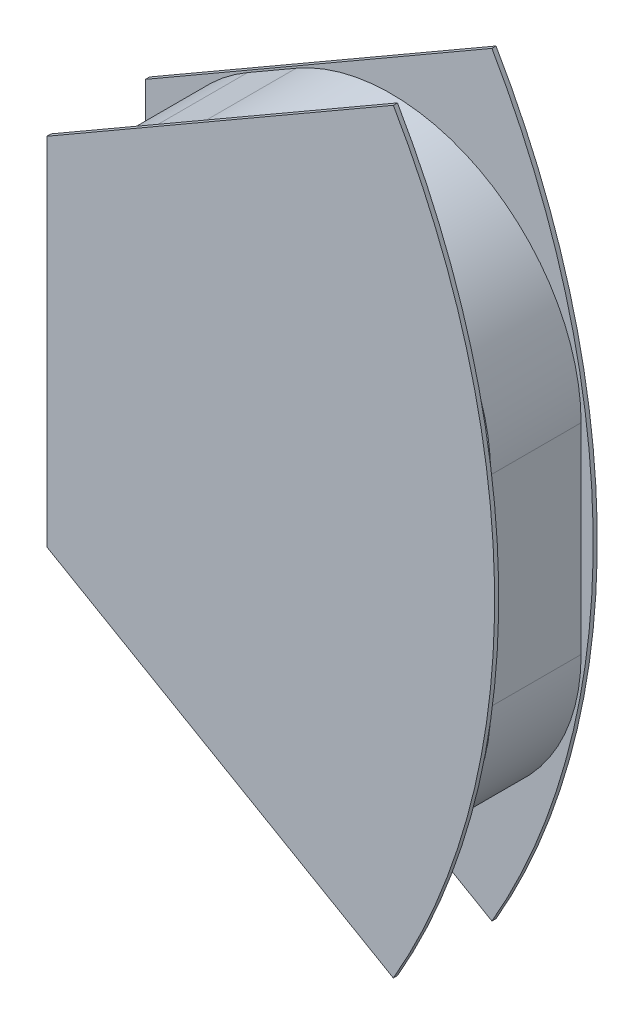
SolidWorks part; units mm, degrees
note: The reader was unsure of these and kept them because the rebuilt part matched: shared geometry of "Sketch3<3>".
ref_plane "Front Plane" through (0, 0, 0) normal (0, 0, 1) x (1, 0, 0)
ref_plane "Top Plane" through (0, 0, 0) normal (0, 1, 0) x (1, 0, 0)
ref_plane "Right Plane" through (0, 0, 0) normal (1, 0, 0) x (0, 0, -1)
sketch "Sketch2" plane through (0, 0, 0) normal (0, 0, 1) x (1, 0, 0)
  line L0 (0, 0) -> (0, -184) construction
  line L1 (-159.3487, -92) -> (0, 0) construction
  line L2 (159.3487, -92) -> (75, -43.3013)
  line L3 (75, 43.3013) -> (75, -43.3013)
  line L4 (0, 0) -> (75, 43.3013) construction
  line L5 (75, 43.3013) -> (159.3487, 92)
  line L6 (75, -43.3013) -> (0, 0) construction
  line L7 (0, 0) -> (-159.3487, 92) construction
  line L8 (0, 184) -> (0, 0) construction
  arc A0 (0, 184) -> (-159.3487, 92) centre (0, 0) ccw construction
  arc A1 (159.3487, 92) -> (0, 184) centre (0, 0) ccw construction
  arc A2 (0, -184) -> (159.3487, -92) centre (0, 0) ccw construction
  arc A3 (159.3487, -92) -> (159.3487, 92) centre (0, 0) ccw
  arc A4 (-159.3487, -92) -> (0, -184) centre (0, 0) ccw construction
  arc A5 (-159.3487, 92) -> (-159.3487, -92) centre (0, 0) ccw construction
  arc A6 (170.1845, -69.9516) -> (170.1845, 69.9516) centre (0, 0) ccw construction
  point P8 (0, -92)
  point P11 (0, -92)
  dimension "D1" = 60
  dimension "D2" = 60
  dimension "D3" = 75
extrude "Boss-Extrude1" add sketch "Sketch2" along normal blind 1 from offset 20
sketch "Sketch3" plane through (0, 0, 21) normal (0, 0, 1) x (1, 0, 0)
  line L0 (124.5, 5.5714) -> (134.3125, 5.5714) construction
  line L1 (123, -18.4752) -> (134.8125, -25.2951)
  line L2 (123, 18.4752) -> (134.8125, 25.2951)
  line L3 (135.3125, -24.4291) -> (135.3125, 24.4291) construction
  line L4 (134.3125, -22.6971) -> (134.3125, 22.6971)
  line L5 (136.3125, -24.4291) -> (136.3125, 24.4291)
  line L6 (134.5742, 22.8482) -> (122.5, 15.8771)
  line L7 (122.5, 15.8771) -> (122.5, -15.8771)
  line L8 (122.5, -15.8771) -> (134.5742, -22.8482)
  line L9 (134.5742, 22.8482) -> (124.5, 17.0318) construction
  line L10 (122.5, 15.8771) -> (122.5, -15.8771) construction
  line L11 (122.5, -15.8771) -> (123.5, -16.4545) construction
  line L12 (0, 0) -> (217.8018, 0) construction
  line L13 (122.5, -15.8771) -> (123.5, -16.4545) construction
  line L14 (123.5, -17.6092) -> (123.5, 17.6092) construction
  line L15 (122.5, -17.6092) -> (122.5, 17.6092)
  line L16 (124.5, -17.0318) -> (124.5, 17.0318)
  line L17 (124.5, 17.0318) -> (134.5742, 22.8482)
  line L18 (124.5, 17.0318) -> (124.5, 17.6092) construction
  line L19 (123.5, 16.4545) -> (122.5, 15.8771) construction
  line L20 (122.5, 15.8771) -> (123.5, 16.4545) construction
  line L21 (123.5, 16.4545) -> (124.5, 17.0318) construction
  line L22 (124.5, 17.0318) -> (123.5, 16.4545) construction
  line L23 (134.3125, 22.6971) -> (134.3125, 24.4291) construction
  line L24 (134.5742, 22.8482) -> (135.3125, 23.2744) construction
  line L25 (135.3125, 23.2744) -> (136.3125, 23.8518) construction
  line L26 (123.5, -16.4545) -> (124.5, -17.0318) construction
  line L27 (124.5, -17.0318) -> (134.3125, -22.6971)
  line L28 (123.5, -16.4545) -> (124.5, -17.0318) construction
  line L29 (124.5, -17.0318) -> (134.3125, -22.6971) construction
  line L30 (124.5, -17.6092) -> (124.5, -17.0318) construction
  line L31 (134.3125, -24.4291) -> (134.3125, -22.6971) construction
  line L32 (134.5742, -22.8482) -> (135.3125, -23.2744) construction
  line L33 (135.3125, -23.2744) -> (136.3125, -23.8518) construction
  line L34 (134.3125, -22.6971) -> (134.5742, -22.8482) construction
  line L35 (134.3125, -22.6971) -> (134.5742, -22.8482) construction
  circle A0 centre (129.4062, 0) radius 3.1
  arc A1 (134.8125, -25.2951) -> (136.3125, -24.4291) centre (135.3125, -24.4291) ccw
  arc A2 (134.5742, -22.8482) -> (134.5742, 22.8482) centre (0, 0) ccw
  arc A3 (134.5742, -22.8482) -> (134.5742, 22.8482) centre (0, 0) ccw construction
  arc A4 (136.3125, 24.4291) -> (134.8125, 25.2951) centre (135.3125, 24.4291) ccw
  arc A5 (122.5, -17.6092) -> (123, -18.4752) centre (123.5, -17.6092) ccw
  arc A6 (123, 18.4752) -> (122.5, 17.6092) centre (123.5, 17.6092) ccw
  arc A7 (124.5, 17.6092) -> (123, 18.4752) centre (123.5, 17.6092) ccw construction
  arc A8 (134.8125, 25.2951) -> (134.3125, 24.4291) centre (135.3125, 24.4291) ccw construction
  arc A9 (123, -18.4752) -> (124.5, -17.6092) centre (123.5, -17.6092) ccw construction
  arc A10 (134.3125, -24.4291) -> (134.8125, -25.2951) centre (135.3125, -24.4291) ccw construction
  point P2 (135.3125, 0)
  point P11 (129.4062, 5.5714)
  point P16 (123.5, 0)
  dimension "D4" = 6.2
  dimension "D2" = 2
  dimension "D3" = 2
  dimension "D1" = 47.5
extrude "Boss-Extrude2" add sketch "Sketch3" along normal blind 22
extrude "Cut-Extrude1" cut sketch "Sketch3<3>" against normal blind 10 contours A0
sketch "Sketch3<3>" plane through (0, 0, 21) normal (0, 0, 1) x (1, 0, 0) same geometry as "Sketch3"
sketch "Sketch4" plane through (0, 0, 21) normal (0, 0, 1) x (1, 0, 0)
  circle A0 centre (129.4062, 0) radius 6.9062
  circle A1 centre (129.4062, 0) radius 3.1
extrude "Boss-Extrude3" add sketch "Sketch4" along normal up to surface (22 mm away) up to face at (129.4062, 0, 43)
sketch "Sketch5" plane through (0, 0, 21) normal (0, 0, 1) x (1, 0, 0)
  line L6 (125, 16.7432) -> (125, 5.9529)
  line L7 (133.8125, 5.9529) -> (133.8125, 21.831)
  line L8 (133.8125, 21.831) -> (125, 16.7432)
  line L9 (125, 16.7432) -> (125, 5.9529)
  line L10 (133.8125, 5.9529) -> (133.8125, 21.831)
  line L11 (133.8125, 21.831) -> (125, 16.7432)
  line L15 (133.8125, -21.831) -> (133.8125, -5.9529)
  line L16 (125, -5.9529) -> (125, -16.7432)
  line L17 (125, -16.7432) -> (133.8125, -21.831)
  line L18 (133.8125, -21.831) -> (133.8125, -5.9529)
  line L19 (125, -5.9529) -> (125, -16.7432)
  line L20 (125, -16.7432) -> (133.8125, -21.831)
  arc A2 (133.8125, 5.9529) -> (125, 5.9529) centre (129.4062, 0) ccw
  arc A3 (133.8125, 5.9529) -> (125, 5.9529) centre (129.4062, 0) ccw
  arc A5 (125, -5.9529) -> (133.8125, -5.9529) centre (129.4062, 0) ccw
  arc A6 (125, -5.9529) -> (133.8125, -5.9529) centre (129.4062, 0) ccw
  dimension "D1" = 0.5
  dimension "D2" = 0.5
extrude "Boss-Extrude4" add sketch "Sketch5" along normal blind 22 from offset 1 separate body
sketch "Sketch6" plane through (0, 0, 44) normal (0, 0, 1) x (1, 0, 0)
  line L3 (159.3487, 92) -> (75, 43.3013)
  line L4 (75, 43.3013) -> (75, -43.3013)
  line L5 (75, -43.3013) -> (159.3487, -92)
  line L6 (159.3487, 92) -> (75, 43.3013)
  line L7 (75, 43.3013) -> (75, -43.3013)
  line L8 (75, -43.3013) -> (159.3487, -92)
  arc A1 (159.3487, -92) -> (159.3487, 92) centre (0, 0) ccw
  arc A2 (159.3487, -92) -> (159.3487, 92) centre (0, 0) ccw
  dimension "D1" = 0
extrude "Boss-Extrude5" add sketch "Sketch6" along normal blind 1
sketch "Sketch7" plane through (0, 0, 21) normal (0, 0, 1) x (1, 0, 0)
  line L13 (77.25, 17.6092) -> (77.25, -17.6092)
  line L14 (100.375, -57.6629) -> (112.1875, -64.4828)
  line L15 (181.5625, -24.4291) -> (181.5625, 24.4291)
  line L16 (112.1875, 64.4828) -> (100.375, 57.6629)
  line L17 (122.25, 17.6092) -> (122.25, -17.6092)
  line L18 (122.875, -18.6917) -> (134.6875, -25.5117)
  line L19 (136.5625, -24.4291) -> (136.5625, 24.4291)
  line L20 (134.6875, 25.5117) -> (122.875, 18.6917)
  line L21 (122.25, 17.6092) -> (122.25, -17.6092)
  line L22 (122.875, -18.6917) -> (134.6875, -25.5117)
  line L23 (136.5625, -24.4291) -> (136.5625, 24.4291)
  line L24 (134.6875, 25.5117) -> (122.875, 18.6917)
  arc A7 (100.375, 57.6629) -> (77.25, 17.6092) centre (123.5, 17.6092) ccw
  arc A8 (77.25, -17.6092) -> (100.375, -57.6629) centre (123.5, -17.6092) ccw
  arc A9 (112.1875, -64.4828) -> (181.5625, -24.4291) centre (135.3125, -24.4291) ccw
  arc A10 (181.5625, 24.4291) -> (112.1875, 64.4828) centre (135.3125, 24.4291) ccw
  arc A11 (122.875, 18.6917) -> (122.25, 17.6092) centre (123.5, 17.6092) ccw
  arc A12 (122.25, -17.6092) -> (122.875, -18.6917) centre (123.5, -17.6092) ccw
  arc A13 (134.6875, -25.5117) -> (136.5625, -24.4291) centre (135.3125, -24.4291) ccw
  arc A14 (136.5625, 24.4291) -> (134.6875, 25.5117) centre (135.3125, 24.4291) ccw
  arc A15 (122.875, 18.6917) -> (122.25, 17.6092) centre (123.5, 17.6092) ccw
  arc A16 (122.25, -17.6092) -> (122.875, -18.6917) centre (123.5, -17.6092) ccw
  arc A17 (134.6875, -25.5117) -> (136.5625, -24.4291) centre (135.3125, -24.4291) ccw
  arc A18 (136.5625, 24.4291) -> (134.6875, 25.5117) centre (135.3125, 24.4291) ccw
  dimension "D1" = 45
  dimension "D2" = 0.25
extrude "Boss-Extrude6" add sketch "Sketch7" along normal blind 22 from offset 0.5 separate body contours L15 A10 L16 A7 L13 A8 L14 A9 A18 L23 A17 L22 A16 L21 A15 L24
sketch "Sketch8" plane through (0, 0, 43.5) normal (0, 0, 1) x (1, 0, 0)
  line L0 (139.8625, -24.4291) -> (139.8625, 24.4291)
  line L1 (133.0375, 28.3695) -> (121.225, 21.5496)
  line L2 (118.95, 17.6092) -> (118.95, -17.6092)
  line L3 (121.225, -21.5496) -> (133.0375, -28.3695)
  line L4 (141.5125, -24.4291) -> (141.5125, 24.4291)
  line L5 (132.2125, 29.7985) -> (120.4, 22.9785)
  line L6 (117.3, 17.6092) -> (117.3, -17.6092)
  line L7 (120.4, -22.9785) -> (132.2125, -29.7985)
  line L8 (122.05, -20.1207) -> (133.8625, -26.9406)
  line L9 (120.6, 17.6092) -> (120.6, -17.6092)
  line L10 (133.8625, 26.9406) -> (122.05, 20.1207)
  line L11 (138.2125, -24.4291) -> (138.2125, 24.4291)
  line L12 (122.05, -20.1207) -> (133.8625, -26.9406)
  line L13 (120.6, 17.6092) -> (120.6, -17.6092)
  line L14 (133.8625, 26.9406) -> (122.05, 20.1207)
  line L15 (138.2125, -24.4291) -> (138.2125, 24.4291)
  line L16 (143.1625, -24.4291) -> (143.1625, 24.4291)
  line L17 (131.3875, 31.2274) -> (119.575, 24.4075)
  line L18 (115.65, 17.6092) -> (115.65, -17.6092)
  line L19 (119.575, -24.4075) -> (131.3875, -31.2274)
  line L20 (144.8125, -24.4291) -> (144.8125, 24.4291)
  line L21 (130.5625, 32.6564) -> (118.75, 25.8364)
  line L22 (114, 17.6092) -> (114, -17.6092)
  line L23 (118.75, -25.8364) -> (130.5625, -32.6564)
  line L24 (146.4625, -24.4291) -> (146.4625, 24.4291)
  line L25 (129.7375, 34.0853) -> (117.925, 27.2654)
  line L26 (112.35, 17.6092) -> (112.35, -17.6092)
  line L27 (117.925, -27.2654) -> (129.7375, -34.0853)
  line L28 (148.1125, -24.4291) -> (148.1125, 24.4291)
  line L29 (128.9125, 35.5142) -> (117.1, 28.6943)
  line L30 (110.7, 17.6092) -> (110.7, -17.6092)
  line L31 (117.1, -28.6943) -> (128.9125, -35.5142)
  line L32 (149.7625, -24.4291) -> (149.7625, 24.4291)
  line L33 (128.0875, 36.9432) -> (116.275, 30.1233)
  line L34 (109.05, 17.6092) -> (109.05, -17.6092)
  line L35 (116.275, -30.1233) -> (128.0875, -36.9432)
  line L36 (151.4125, -24.4291) -> (151.4125, 24.4291)
  line L37 (127.2625, 38.3721) -> (115.45, 31.5522)
  line L38 (107.4, 17.6092) -> (107.4, -17.6092)
  line L39 (115.45, -31.5522) -> (127.2625, -38.3721)
  line L40 (153.0625, -24.4291) -> (153.0625, 24.4291)
  line L41 (126.4375, 39.8011) -> (114.625, 32.9811)
  line L42 (105.75, 17.6092) -> (105.75, -17.6092)
  line L43 (114.625, -32.9811) -> (126.4375, -39.8011)
  line L44 (154.7125, -24.4291) -> (154.7125, 24.4291)
  line L45 (125.6125, 41.23) -> (113.8, 34.4101)
  line L46 (104.1, 17.6092) -> (104.1, -17.6092)
  line L47 (113.8, -34.4101) -> (125.6125, -41.23)
  line L48 (156.3625, -24.4291) -> (156.3625, 24.4291)
  line L49 (124.7875, 42.659) -> (112.975, 35.839)
  line L50 (102.45, 17.6092) -> (102.45, -17.6092)
  line L51 (112.975, -35.839) -> (124.7875, -42.659)
  line L52 (158.0125, -24.4291) -> (158.0125, 24.4291)
  line L53 (123.9625, 44.0879) -> (112.15, 37.268)
  line L54 (100.8, 17.6092) -> (100.8, -17.6092)
  line L55 (112.15, -37.268) -> (123.9625, -44.0879)
  line L56 (159.6625, -24.4291) -> (159.6625, 24.4291)
  line L57 (123.1375, 45.5168) -> (111.325, 38.6969)
  line L58 (99.15, 17.6092) -> (99.15, -17.6092)
  line L59 (111.325, -38.6969) -> (123.1375, -45.5168)
  line L60 (161.3125, -24.4291) -> (161.3125, 24.4291)
  line L61 (122.3125, 46.9458) -> (110.5, 40.1258)
  line L62 (97.5, 17.6092) -> (97.5, -17.6092)
  line L63 (110.5, -40.1258) -> (122.3125, -46.9458)
  line L64 (162.9625, -24.4291) -> (162.9625, 24.4291)
  line L65 (121.4875, 48.3747) -> (109.675, 41.5548)
  line L66 (95.85, 17.6092) -> (95.85, -17.6092)
  line L67 (109.675, -41.5548) -> (121.4875, -48.3747)
  line L68 (94.2, 17.6092) -> (94.2, -17.6092)
  line L69 (108.85, -42.9837) -> (120.6625, -49.8037)
  line L70 (164.6125, -24.4291) -> (164.6125, 24.4291)
  line L71 (120.6625, 49.8037) -> (108.85, 42.9837)
  line L72 (92.55, 17.6092) -> (92.55, -17.6092)
  line L73 (108.025, -44.4127) -> (119.8375, -51.2326)
  line L74 (166.2625, -24.4291) -> (166.2625, 24.4291)
  line L75 (119.8375, 51.2326) -> (108.025, 44.4127)
  line L76 (90.9, 17.6092) -> (90.9, -17.6092)
  line L77 (107.2, -45.8416) -> (119.0125, -52.6616)
  line L78 (167.9125, -24.4291) -> (167.9125, 24.4291)
  line L79 (119.0125, 52.6616) -> (107.2, 45.8416)
  line L80 (89.25, 17.6092) -> (89.25, -17.6092)
  line L81 (106.375, -47.2706) -> (118.1875, -54.0905)
  line L82 (169.5625, -24.4291) -> (169.5625, 24.4291)
  line L83 (118.1875, 54.0905) -> (106.375, 47.2706)
  line L84 (87.6, 17.6092) -> (87.6, -17.6092)
  line L85 (105.55, -48.6995) -> (117.3625, -55.5194)
  line L86 (171.2125, -24.4291) -> (171.2125, 24.4291)
  line L87 (117.3625, 55.5194) -> (105.55, 48.6995)
  line L88 (85.95, 17.6092) -> (85.95, -17.6092)
  line L89 (104.725, -50.1284) -> (116.5375, -56.9484)
  line L90 (172.8625, -24.4291) -> (172.8625, 24.4291)
  line L91 (116.5375, 56.9484) -> (104.725, 50.1284)
  line L92 (84.3, 17.6092) -> (84.3, -17.6092)
  line L93 (103.9, -51.5574) -> (115.7125, -58.3773)
  line L94 (174.5125, -24.4291) -> (174.5125, 24.4291)
  line L95 (115.7125, 58.3773) -> (103.9, 51.5574)
  line L96 (82.65, 17.6092) -> (82.65, -17.6092)
  line L97 (103.075, -52.9863) -> (114.8875, -59.8063)
  line L98 (176.1625, -24.4291) -> (176.1625, 24.4291)
  line L99 (114.8875, 59.8063) -> (103.075, 52.9863)
  line L100 (81, 17.6092) -> (81, -17.6092)
  line L101 (102.25, -54.4153) -> (114.0625, -61.2352)
  line L102 (177.8125, -24.4291) -> (177.8125, 24.4291)
  line L103 (114.0625, 61.2352) -> (102.25, 54.4153)
  line L104 (79.35, 17.6092) -> (79.35, -17.6092)
  line L105 (101.425, -55.8442) -> (113.2375, -62.6641)
  line L106 (179.4625, -24.4291) -> (179.4625, 24.4291)
  line L107 (113.2375, 62.6641) -> (101.425, 55.8442)
  arc A0 (133.0375, -28.3695) -> (139.8625, -24.4291) centre (135.3125, -24.4291) ccw
  arc A1 (139.8625, 24.4291) -> (133.0375, 28.3695) centre (135.3125, 24.4291) ccw
  arc A2 (121.225, 21.5496) -> (118.95, 17.6092) centre (123.5, 17.6092) ccw
  arc A3 (118.95, -17.6092) -> (121.225, -21.5496) centre (123.5, -17.6092) ccw
  arc A4 (132.2125, -29.7985) -> (141.5125, -24.4291) centre (135.3125, -24.4291) ccw
  arc A5 (141.5125, 24.4291) -> (132.2125, 29.7985) centre (135.3125, 24.4291) ccw
  arc A6 (120.4, 22.9785) -> (117.3, 17.6092) centre (123.5, 17.6092) ccw
  arc A7 (117.3, -17.6092) -> (120.4, -22.9785) centre (123.5, -17.6092) ccw
  arc A8 (133.8625, -26.9406) -> (138.2125, -24.4291) centre (135.3125, -24.4291) ccw
  arc A9 (120.6, -17.6092) -> (122.05, -20.1207) centre (123.5, -17.6092) ccw
  arc A10 (122.05, 20.1207) -> (120.6, 17.6092) centre (123.5, 17.6092) ccw
  arc A11 (138.2125, 24.4291) -> (133.8625, 26.9406) centre (135.3125, 24.4291) ccw
  arc A12 (133.8625, -26.9406) -> (138.2125, -24.4291) centre (135.3125, -24.4291) ccw
  arc A13 (120.6, -17.6092) -> (122.05, -20.1207) centre (123.5, -17.6092) ccw
  arc A14 (122.05, 20.1207) -> (120.6, 17.6092) centre (123.5, 17.6092) ccw
  arc A15 (138.2125, 24.4291) -> (133.8625, 26.9406) centre (135.3125, 24.4291) ccw
  arc A16 (131.3875, -31.2274) -> (143.1625, -24.4291) centre (135.3125, -24.4291) ccw
  arc A17 (143.1625, 24.4291) -> (131.3875, 31.2274) centre (135.3125, 24.4291) ccw
  arc A18 (119.575, 24.4075) -> (115.65, 17.6092) centre (123.5, 17.6092) ccw
  arc A19 (115.65, -17.6092) -> (119.575, -24.4075) centre (123.5, -17.6092) ccw
  arc A20 (130.5625, -32.6564) -> (144.8125, -24.4291) centre (135.3125, -24.4291) ccw
  arc A21 (144.8125, 24.4291) -> (130.5625, 32.6564) centre (135.3125, 24.4291) ccw
  arc A22 (118.75, 25.8364) -> (114, 17.6092) centre (123.5, 17.6092) ccw
  arc A23 (114, -17.6092) -> (118.75, -25.8364) centre (123.5, -17.6092) ccw
  arc A24 (129.7375, -34.0853) -> (146.4625, -24.4291) centre (135.3125, -24.4291) ccw
  arc A25 (146.4625, 24.4291) -> (129.7375, 34.0853) centre (135.3125, 24.4291) ccw
  arc A26 (117.925, 27.2654) -> (112.35, 17.6092) centre (123.5, 17.6092) ccw
  arc A27 (112.35, -17.6092) -> (117.925, -27.2654) centre (123.5, -17.6092) ccw
  arc A28 (128.9125, -35.5142) -> (148.1125, -24.4291) centre (135.3125, -24.4291) ccw
  arc A29 (148.1125, 24.4291) -> (128.9125, 35.5142) centre (135.3125, 24.4291) ccw
  arc A30 (117.1, 28.6943) -> (110.7, 17.6092) centre (123.5, 17.6092) ccw
  arc A31 (110.7, -17.6092) -> (117.1, -28.6943) centre (123.5, -17.6092) ccw
  arc A32 (128.0875, -36.9432) -> (149.7625, -24.4291) centre (135.3125, -24.4291) ccw
  arc A33 (149.7625, 24.4291) -> (128.0875, 36.9432) centre (135.3125, 24.4291) ccw
  arc A34 (116.275, 30.1233) -> (109.05, 17.6092) centre (123.5, 17.6092) ccw
  arc A35 (109.05, -17.6092) -> (116.275, -30.1233) centre (123.5, -17.6092) ccw
  arc A36 (127.2625, -38.3721) -> (151.4125, -24.4291) centre (135.3125, -24.4291) ccw
  arc A37 (151.4125, 24.4291) -> (127.2625, 38.3721) centre (135.3125, 24.4291) ccw
  arc A38 (115.45, 31.5522) -> (107.4, 17.6092) centre (123.5, 17.6092) ccw
  arc A39 (107.4, -17.6092) -> (115.45, -31.5522) centre (123.5, -17.6092) ccw
  arc A40 (126.4375, -39.8011) -> (153.0625, -24.4291) centre (135.3125, -24.4291) ccw
  arc A41 (153.0625, 24.4291) -> (126.4375, 39.8011) centre (135.3125, 24.4291) ccw
  arc A42 (114.625, 32.9811) -> (105.75, 17.6092) centre (123.5, 17.6092) ccw
  arc A43 (105.75, -17.6092) -> (114.625, -32.9811) centre (123.5, -17.6092) ccw
  arc A44 (125.6125, -41.23) -> (154.7125, -24.4291) centre (135.3125, -24.4291) ccw
  arc A45 (154.7125, 24.4291) -> (125.6125, 41.23) centre (135.3125, 24.4291) ccw
  arc A46 (113.8, 34.4101) -> (104.1, 17.6092) centre (123.5, 17.6092) ccw
  arc A47 (104.1, -17.6092) -> (113.8, -34.4101) centre (123.5, -17.6092) ccw
  arc A48 (124.7875, -42.659) -> (156.3625, -24.4291) centre (135.3125, -24.4291) ccw
  arc A49 (156.3625, 24.4291) -> (124.7875, 42.659) centre (135.3125, 24.4291) ccw
  arc A50 (112.975, 35.839) -> (102.45, 17.6092) centre (123.5, 17.6092) ccw
  arc A51 (102.45, -17.6092) -> (112.975, -35.839) centre (123.5, -17.6092) ccw
  arc A52 (123.9625, -44.0879) -> (158.0125, -24.4291) centre (135.3125, -24.4291) ccw
  arc A53 (158.0125, 24.4291) -> (123.9625, 44.0879) centre (135.3125, 24.4291) ccw
  arc A54 (112.15, 37.268) -> (100.8, 17.6092) centre (123.5, 17.6092) ccw
  arc A55 (100.8, -17.6092) -> (112.15, -37.268) centre (123.5, -17.6092) ccw
  arc A56 (123.1375, -45.5168) -> (159.6625, -24.4291) centre (135.3125, -24.4291) ccw
  arc A57 (159.6625, 24.4291) -> (123.1375, 45.5168) centre (135.3125, 24.4291) ccw
  arc A58 (111.325, 38.6969) -> (99.15, 17.6092) centre (123.5, 17.6092) ccw
  arc A59 (99.15, -17.6092) -> (111.325, -38.6969) centre (123.5, -17.6092) ccw
  arc A60 (122.3125, -46.9458) -> (161.3125, -24.4291) centre (135.3125, -24.4291) ccw
  arc A61 (161.3125, 24.4291) -> (122.3125, 46.9458) centre (135.3125, 24.4291) ccw
  arc A62 (110.5, 40.1258) -> (97.5, 17.6092) centre (123.5, 17.6092) ccw
  arc A63 (97.5, -17.6092) -> (110.5, -40.1258) centre (123.5, -17.6092) ccw
  arc A64 (121.4875, -48.3747) -> (162.9625, -24.4291) centre (135.3125, -24.4291) ccw
  arc A65 (162.9625, 24.4291) -> (121.4875, 48.3747) centre (135.3125, 24.4291) ccw
  arc A66 (109.675, 41.5548) -> (95.85, 17.6092) centre (123.5, 17.6092) ccw
  arc A67 (95.85, -17.6092) -> (109.675, -41.5548) centre (123.5, -17.6092) ccw
  arc A68 (108.85, 42.9837) -> (94.2, 17.6092) centre (123.5, 17.6092) ccw
  arc A69 (94.2, -17.6092) -> (108.85, -42.9837) centre (123.5, -17.6092) ccw
  arc A70 (120.6625, -49.8037) -> (164.6125, -24.4291) centre (135.3125, -24.4291) ccw
  arc A71 (164.6125, 24.4291) -> (120.6625, 49.8037) centre (135.3125, 24.4291) ccw
  arc A72 (108.025, 44.4127) -> (92.55, 17.6092) centre (123.5, 17.6092) ccw
  arc A73 (92.55, -17.6092) -> (108.025, -44.4127) centre (123.5, -17.6092) ccw
  arc A74 (119.8375, -51.2326) -> (166.2625, -24.4291) centre (135.3125, -24.4291) ccw
  arc A75 (166.2625, 24.4291) -> (119.8375, 51.2326) centre (135.3125, 24.4291) ccw
  arc A76 (107.2, 45.8416) -> (90.9, 17.6092) centre (123.5, 17.6092) ccw
  arc A77 (90.9, -17.6092) -> (107.2, -45.8416) centre (123.5, -17.6092) ccw
  arc A78 (119.0125, -52.6616) -> (167.9125, -24.4291) centre (135.3125, -24.4291) ccw
  arc A79 (167.9125, 24.4291) -> (119.0125, 52.6616) centre (135.3125, 24.4291) ccw
  arc A80 (106.375, 47.2706) -> (89.25, 17.6092) centre (123.5, 17.6092) ccw
  arc A81 (89.25, -17.6092) -> (106.375, -47.2706) centre (123.5, -17.6092) ccw
  arc A82 (118.1875, -54.0905) -> (169.5625, -24.4291) centre (135.3125, -24.4291) ccw
  arc A83 (169.5625, 24.4291) -> (118.1875, 54.0905) centre (135.3125, 24.4291) ccw
  arc A84 (105.55, 48.6995) -> (87.6, 17.6092) centre (123.5, 17.6092) ccw
  arc A85 (87.6, -17.6092) -> (105.55, -48.6995) centre (123.5, -17.6092) ccw
  arc A86 (117.3625, -55.5194) -> (171.2125, -24.4291) centre (135.3125, -24.4291) ccw
  arc A87 (171.2125, 24.4291) -> (117.3625, 55.5194) centre (135.3125, 24.4291) ccw
  arc A88 (104.725, 50.1284) -> (85.95, 17.6092) centre (123.5, 17.6092) ccw
  arc A89 (85.95, -17.6092) -> (104.725, -50.1284) centre (123.5, -17.6092) ccw
  arc A90 (116.5375, -56.9484) -> (172.8625, -24.4291) centre (135.3125, -24.4291) ccw
  arc A91 (172.8625, 24.4291) -> (116.5375, 56.9484) centre (135.3125, 24.4291) ccw
  arc A92 (103.9, 51.5574) -> (84.3, 17.6092) centre (123.5, 17.6092) ccw
  arc A93 (84.3, -17.6092) -> (103.9, -51.5574) centre (123.5, -17.6092) ccw
  arc A94 (115.7125, -58.3773) -> (174.5125, -24.4291) centre (135.3125, -24.4291) ccw
  arc A95 (174.5125, 24.4291) -> (115.7125, 58.3773) centre (135.3125, 24.4291) ccw
  arc A96 (103.075, 52.9863) -> (82.65, 17.6092) centre (123.5, 17.6092) ccw
  arc A97 (82.65, -17.6092) -> (103.075, -52.9863) centre (123.5, -17.6092) ccw
  arc A98 (114.8875, -59.8063) -> (176.1625, -24.4291) centre (135.3125, -24.4291) ccw
  arc A99 (176.1625, 24.4291) -> (114.8875, 59.8063) centre (135.3125, 24.4291) ccw
  arc A100 (102.25, 54.4153) -> (81, 17.6092) centre (123.5, 17.6092) ccw
  arc A101 (81, -17.6092) -> (102.25, -54.4153) centre (123.5, -17.6092) ccw
  arc A102 (114.0625, -61.2352) -> (177.8125, -24.4291) centre (135.3125, -24.4291) ccw
  arc A103 (177.8125, 24.4291) -> (114.0625, 61.2352) centre (135.3125, 24.4291) ccw
  arc A104 (101.425, 55.8442) -> (79.35, 17.6092) centre (123.5, 17.6092) ccw
  arc A105 (79.35, -17.6092) -> (101.425, -55.8442) centre (123.5, -17.6092) ccw
  arc A106 (113.2375, -62.6641) -> (179.4625, -24.4291) centre (135.3125, -24.4291) ccw
  arc A107 (179.4625, 24.4291) -> (113.2375, 62.6641) centre (135.3125, 24.4291) ccw
  dimension "D1" = 1.65
  dimension "D2" = 1.65
  dimension "D3" = 1.65
  dimension "D4" = 1.65
  dimension "D5" = 1.65
  dimension "D6" = 1.65
  dimension "D7" = 1.65
  dimension "D8" = 1.65
  dimension "D9" = 1.65
  dimension "D10" = 1.65
  dimension "D11" = 1.65
  dimension "D12" = 1.65
  dimension "D13" = 1.65
  dimension "D14" = 1.65
  dimension "D15" = 1.65
  dimension "D16" = 1.65
  dimension "D17" = 1.65
  dimension "D18" = 1.65
  dimension "D19" = 1.65
  dimension "D20" = 1.65
  dimension "D21" = 1.65
  dimension "D22" = 1.65
  dimension "D23" = 1.65
  dimension "D24" = 1.65
  dimension "D25" = 1.65
  dimension "D26" = 1.65
extrude "Cut-Extrude-Thin3" cut sketch "Sketch8" against normal blind 22 thin contours A12 L15 A15 L14 A14 L13 A13 L12 | L2 A3 L3 A0 L0 A1 L1 A2 | L6 A7 L7 A4 L4 A5 L5 A6 | L18 A19 L19 A16 L16 A17 L17 A18 | L22 A23 L23 A20 L20 A21 L21 A22 | L26 A27 L27 A24 L24 A25 L25 A26 | L30 A31 L31 A28 L28 A29 L29 A30 | L34 A35 L35 A32 L32 A33 L33 A34 | L38 A39 L39 A36 L36 A37 L37 A38 | L42 A43 L43 A40 L40 A41 L41 A42 | L46 A47 L47 A44 L44 A45 L45 A46 | L50 A51 L51 A48 L48 A49 L49 A50 | L54 A55 L55 A52 L52 A53 L53 A54 | L58 A59 L59 A56 L56 A57 L57 A58 | L62 A63 L63 A60 L60 A61 L61 A62 | L66 A67 L67 A64 L64 A65 L65 A66 | L68 A69 L69 A70 L70 A71 L71 A68 | L72 A73 L73 A74 L74 A75 L75 A72 | L76 A77 L77 A78 L78 A79 L79 A76 | L80 A81 L81 A82 L82 A83 L83 A80 | L84 A85 L85 A86 L86 A87 L87 A84 | L88 A89 L89 A90 L90 A91 L91 A88 | L92 A93 L93 A94 L94 A95 L95 A92 | L96 A97 L97 A98 L98 A99 L99 A96 | L100 A101 L101 A102 L102 A103 L103 A100 | L104 A105 L105 A106 L106 A107 L107 A104 thin type mid plane wall 0.1
